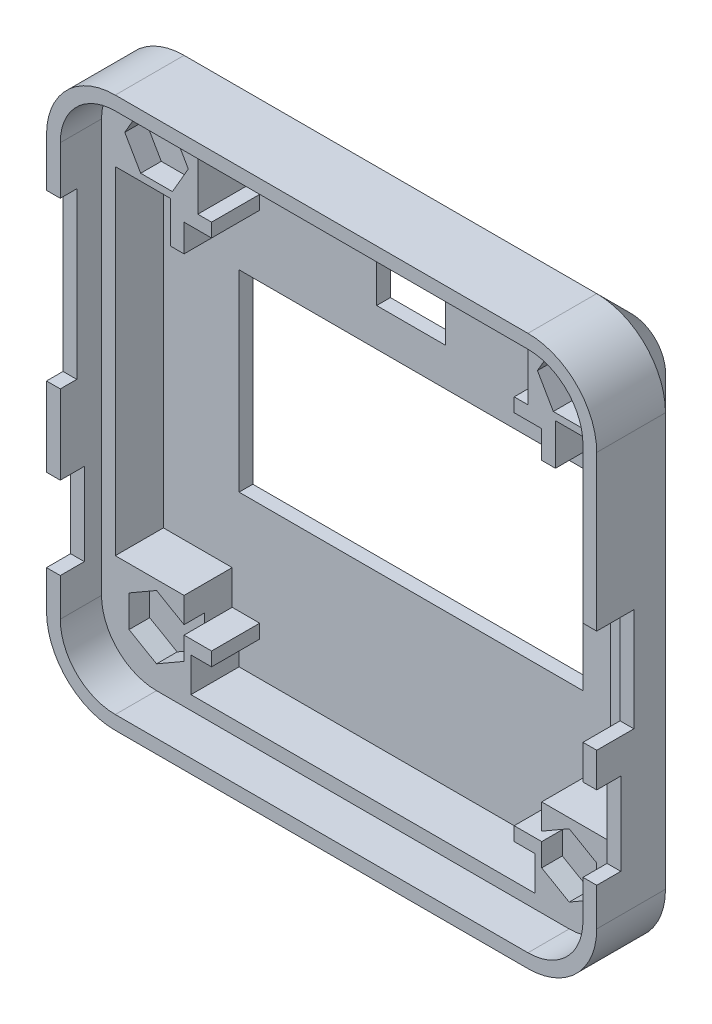
SolidWorks part; units mm, degrees
ref_plane "前基準面" through (0, 0, 0) normal (0, 0, 1) x (1, 0, 0)
ref_plane "上基準面" through (0, 0, 0) normal (0, 1, 0) x (1, 0, 0)
ref_plane "右基準面" through (0, 0, 0) normal (1, 0, 0) x (0, 0, -1)
sketch "草圖2" plane through (0, 0, -2.5) normal (0, 0, -1) x (-1, 0, 0)
  line L1 (0, 0) -> (1.8142, 0) construction
  line L2 (-15, -18.5) -> (15, -18.5)
  line L3 (-20, -13.5) -> (-20, 16.5)
  line L4 (-15, 21.5) -> (15, 21.5)
  line L5 (20, -13.5) -> (20, 16.5)
  line L6 (-20, -18.5) -> (20, 21.5) construction
  line L7 (-20, 21.5) -> (20, -18.5) construction
  arc A0 (-20, 16.5) -> (-15, 21.5) centre (-15, 16.5) cw
  arc A1 (15, -18.5) -> (20, -13.5) centre (15, -13.5) ccw
  arc A2 (-15, -18.5) -> (-20, -13.5) centre (-15, -13.5) cw
  arc A3 (15, 21.5) -> (20, 16.5) centre (15, 16.5) cw
  point P2 (0, 1.5)
  dimension "D3" = 5
  dimension "D1" = 40
  dimension "D2" = 40
  dimension "D4" = 1.5
extrude "填料-伸長1" add sketch "草圖2" along normal blind 1
sketch "草圖3" plane through (0, 0, -3.5) normal (0, 0, -1) x (-1, 0, 0)
  line L0 (0, 0) -> (5.3132, 0) construction
  line L1 (-12.5, -5.5) -> (12.5, -5.5)
  line L2 (-12.5, -5.5) -> (-12.5, 8.5)
  line L3 (-12.5, 8.5) -> (12.5, 8.5)
  line L4 (12.5, -5.5) -> (12.5, 8.5)
  line L5 (-12.5, -5.5) -> (12.5, 8.5) construction
  line L6 (-12.5, 8.5) -> (12.5, -5.5) construction
  point P0 (0, 1.5)
  dimension "D1" = 14
  dimension "D2" = 25
  dimension "D3" = 1.5
extrude "除料-伸長1" cut sketch "草圖3" against normal through all
sketch "草圖4" plane through (0, 0, -2.5) normal (0, 0, 1) x (1, 0, 0)
  line L16 (15, -18.5) -> (-15, -18.5) construction
  line L17 (-20, -13.5) -> (-20, 16.5) construction
  line L18 (-15, 21.5) -> (15, 21.5) construction
  line L19 (20, 16.5) -> (20, -13.5) construction
  line L20 (19, -13.5) -> (19, 16.5)
  line L21 (15, 20.5) -> (-15, 20.5)
  line L22 (-19, 16.5) -> (-19, -13.5)
  line L23 (-15, -17.5) -> (15, -17.5)
  line L24 (19, -13.5) -> (19, 16.5)
  line L25 (15, 20.5) -> (-15, 20.5)
  line L26 (-19, 16.5) -> (-19, -13.5)
  line L27 (-15, -17.5) -> (15, -17.5)
  line L28 (15, -18.5) -> (-15, -18.5)
  line L29 (-20, -13.5) -> (-20, 16.5)
  line L30 (-15, 21.5) -> (15, 21.5)
  line L31 (20, 16.5) -> (20, -13.5)
  arc A20 (-20, -13.5) -> (-15, -18.5) centre (-15, -13.5) ccw construction
  arc A21 (-15, 21.5) -> (-20, 16.5) centre (-15, 16.5) ccw construction
  arc A22 (20, 16.5) -> (15, 21.5) centre (15, 16.5) ccw construction
  arc A23 (15, -18.5) -> (20, -13.5) centre (15, -13.5) ccw construction
  arc A24 (19, 16.5) -> (15, 20.5) centre (15, 16.5) ccw
  arc A25 (-15, 20.5) -> (-19, 16.5) centre (-15, 16.5) ccw
  arc A26 (-19, -13.5) -> (-15, -17.5) centre (-15, -13.5) ccw
  arc A27 (15, -17.5) -> (19, -13.5) centre (15, -13.5) ccw
  arc A28 (19, 16.5) -> (15, 20.5) centre (15, 16.5) ccw
  arc A29 (-15, 20.5) -> (-19, 16.5) centre (-15, 16.5) ccw
  arc A30 (-19, -13.5) -> (-15, -17.5) centre (-15, -13.5) ccw
  arc A31 (15, -17.5) -> (19, -13.5) centre (15, -13.5) ccw
  arc A32 (-20, -13.5) -> (-15, -18.5) centre (-15, -13.5) ccw
  arc A33 (-15, 21.5) -> (-20, 16.5) centre (-15, 16.5) ccw
  arc A34 (20, 16.5) -> (15, 21.5) centre (15, 16.5) ccw
  arc A35 (15, -18.5) -> (20, -13.5) centre (15, -13.5) ccw
  dimension "D1" = 1
extrude "填料-伸長2" add sketch "草圖4" along normal blind 6.5
sketch "草圖5" plane through (0, 0, -2.5) normal (0, 0, 1) x (1, 0, 0)
  line L0 (18, -13.5) -> (18, 16.5)
  line L1 (15, 19.5) -> (-15, 19.5)
  line L2 (-18, 16.5) -> (-18, -13.5)
  line L3 (-15, -16.5) -> (15, -16.5)
  line L4 (19, -13.5) -> (19, 16.5)
  line L5 (15, 20.5) -> (-15, 20.5)
  line L6 (-19, 16.5) -> (-19, -13.5)
  line L7 (-15, -17.5) -> (15, -17.5)
  line L8 (19, -13.5) -> (19, 16.5)
  line L9 (15, 20.5) -> (-15, 20.5)
  line L10 (-19, 16.5) -> (-19, -13.5)
  line L11 (-15, -17.5) -> (15, -17.5)
  arc A0 (15, -16.5) -> (18, -13.5) centre (15, -13.5) ccw
  arc A1 (18, 16.5) -> (15, 19.5) centre (15, 16.5) ccw
  arc A2 (-15, 19.5) -> (-18, 16.5) centre (-15, 16.5) ccw
  arc A3 (-18, -13.5) -> (-15, -16.5) centre (-15, -13.5) ccw
  arc A4 (15, -17.5) -> (19, -13.5) centre (15, -13.5) ccw
  arc A5 (19, 16.5) -> (15, 20.5) centre (15, 16.5) ccw
  arc A6 (-15, 20.5) -> (-19, 16.5) centre (-15, 16.5) ccw
  arc A7 (-19, -13.5) -> (-15, -17.5) centre (-15, -13.5) ccw
  arc A8 (15, -17.5) -> (19, -13.5) centre (15, -13.5) ccw
  arc A9 (19, 16.5) -> (15, 20.5) centre (15, 16.5) ccw
  arc A10 (-15, 20.5) -> (-19, 16.5) centre (-15, 16.5) ccw
  arc A11 (-19, -13.5) -> (-15, -17.5) centre (-15, -13.5) ccw
  dimension "D1" = 0
  dimension "D2" = 1
extrude "填料-伸長3" add sketch "草圖5" along normal blind 3.5
sketch "草圖6" plane through (0, 0, -2.5) normal (0, 0, 1) x (1, 0, 0)
  line L0 (14, -14) -> (14, -10.5)
  line L1 (14, 14) -> (11, 14)
  line L2 (-14, 14) -> (-14, 11)
  line L3 (-14, -14) -> (-11, -14)
  line L4 (-13, -13) -> (13, -13)
  line L5 (-13, 13) -> (-13, -13)
  line L6 (13, 13) -> (-13, 13)
  line L7 (13, -13) -> (13, 13)
  line L8 (-13, -13) -> (-11, -13)
  line L9 (-13, 13) -> (-13, 11)
  line L10 (13, 13) -> (11, 13)
  line L11 (13, -13) -> (13, -10.5)
  line L12 (-11, 14) -> (-11, 13)
  line L13 (-13, 11) -> (-14, 11)
  line L14 (-13, -10.5) -> (-14, -10.5)
  line L15 (-11, -13) -> (-11, -14)
  line L16 (11, -13) -> (11, -14)
  line L17 (14, -10.5) -> (13, -10.5)
  line L18 (14, 11) -> (13, 11)
  line L19 (11, 14) -> (11, 13)
  line L20 (11, -14) -> (14, -14)
  line L21 (-14, -14) -> (14, -14) construction
  line L22 (11, -13) -> (13, -13)
  line L23 (-13, -13) -> (13, -13) construction
  line L24 (14, 11) -> (14, 14)
  line L25 (14, -14) -> (14, 14) construction
  line L26 (13, 11) -> (13, 13)
  line L27 (13, -13) -> (13, 13) construction
  line L28 (-11, 13) -> (-13, 13)
  line L29 (13, 13) -> (-13, 13) construction
  line L30 (-11, 14) -> (-14, 14)
  line L31 (14, 14) -> (-14, 14) construction
  line L32 (-13, -10.5) -> (-13, -13)
  line L33 (-13, 13) -> (-13, -13) construction
  line L34 (-14, -10.5) -> (-14, -14)
  line L35 (-14, 14) -> (-14, -14) construction
  dimension "D3" = 3
  dimension "D4" = 3
  dimension "D5" = 3.5
  dimension "D6" = 3
  dimension "D7" = 3
  dimension "D8" = 3.5
  dimension "D9" = 3
  dimension "D10" = 3
  dimension "D1" = 0
  dimension "D2" = 1
extrude "填料-伸長4" add sketch "草圖6" along normal blind 3.5
chamfer "導角1" distance 2.5 angle 45 8 edges at (-20, 1.5, -3.5) (-18.5355, 20.0355, -3.5) (-18.5355, -17.0355, -3.5) (0, 21.5, -3.5) (0, -18.5, -3.5) (18.5355, 20.0355, -3.5) (18.5355, -17.0355, -3.5) (20, 1.5, -3.5)
sketch "草圖7" plane through (0, 0, -2.5) normal (0, 0, 1) x (1, 0, 0)
  line L0 (-12, 19.5) -> (-12, 14)
  line L1 (15, 19.5) -> (-15, 19.5) construction
  line L2 (-11, 14) -> (-14, 14) construction
  line L3 (-12, 14) -> (-18, 14)
  line L4 (-18, 16.5) -> (-18, -13.5) construction
  line L5 (15, 19.5) -> (-15, 19.5) construction
  line L6 (-18, 16.5) -> (-18, -13.5) construction
  line L7 (-12, 19.5) -> (-15, 19.5)
  line L8 (-18, 16.5) -> (-18, 14)
  arc A0 (-15, 19.5) -> (-18, 16.5) centre (-15, 16.5) ccw construction
  arc A1 (-15, 19.5) -> (-18, 16.5) centre (-15, 16.5) ccw
  dimension "D1" = 6
extrude "填料-伸長5" add sketch "草圖7" along normal up to surface (3.5 mm away) up to face at (0, 1.5, 1)
sketch "草圖8" plane through (0, 0, -2.5) normal (0, 0, 1) x (1, 0, 0)
  line L0 (-12.5, -16.5) -> (-12.5, -14)
  line L1 (-15, -16.5) -> (15, -16.5) construction
  line L2 (-14, -14) -> (-11, -14) construction
  line L3 (-14, -10.5) -> (-18, -10.5)
  line L5 (-18, 14) -> (-18, -13.5) construction
  line L6 (-14, -14) -> (-11, -14) construction
  line L7 (-14, -10.5) -> (-14, -14) construction
  line L8 (-14, -14) -> (-12.5, -14)
  line L9 (-14, -10.5) -> (-14, -14)
  line L10 (-15, -16.5) -> (15, -16.5) construction
  line L11 (-18, 14) -> (-18, -13.5) construction
  line L12 (-15, -16.5) -> (-12.5, -16.5)
  line L13 (-18, -10.5) -> (-18, -13.5)
  arc A0 (-18, -13.5) -> (-15, -16.5) centre (-15, -13.5) ccw construction
  arc A1 (-18, -13.5) -> (-15, -16.5) centre (-15, -13.5) ccw
  dimension "D1" = 5.5
  dimension "D2" = 6
extrude "填料-伸長6" add sketch "草圖8" along normal up to surface (3.5 mm away) up to face at (0, 1.5, 1)
mirror "鏡射2" about plane through (0, 0, 0) normal (1, 0, 0) of "填料-伸長6", "填料-伸長5"
sketch "草圖10" plane through (0, 0, 1) normal (0, 0, 1) x (1, 0, 0)
  line L0 (-13, -13) -> (-13, -10.5) construction
  line L1 (-15, -15.8094) -> (-13, -14.6547)
  line L2 (-13, -14.6547) -> (-13, -12.3453)
  line L3 (-13, -12.3453) -> (-15, -11.1906)
  line L4 (-15, -11.1906) -> (-17, -12.3453)
  line L5 (-17, -12.3453) -> (-17, -14.6547)
  line L6 (-17, -14.6547) -> (-15, -15.8094)
  circle A0 centre (-15, -13.5) radius 2 construction
  dimension "D1" = 4
extrude "除料-伸長2" cut sketch "草圖10" against normal blind 1.5
sketch "草圖11" plane through (0, 0, 1) normal (0, 0, 1) x (1, 0, 0)
  line L0 (-18, 14) -> (-14, 14) construction
  line L1 (-17.3094, 16.5) -> (-16.1547, 14.5)
  line L2 (-16.1547, 14.5) -> (-13.8453, 14.5)
  line L3 (-13.8453, 14.5) -> (-12.6906, 16.5)
  line L4 (-12.6906, 16.5) -> (-13.8453, 18.5)
  line L5 (-13.8453, 18.5) -> (-16.1547, 18.5)
  line L6 (-16.1547, 18.5) -> (-17.3094, 16.5)
  circle A0 centre (-15, 16.5) radius 2 construction
  dimension "D1" = 4
extrude "除料-伸長3" cut sketch "草圖11" against normal blind 1.5
mirror "鏡射3" about plane through (0, 0, 0) normal (1, 0, 0) of "除料-伸長3", "除料-伸長2"
sketch "草圖12" plane through (20, 0, 0) normal (1, 0, 0) x (0, 0, -1)
  line L0 (-4, 1.5) -> (8.2769, 1.5) construction
  line L1 (-4, -13.5) -> (-4, 16.5) construction
  line L2 (1, -13.5) -> (-4, -13.5) construction
  line L3 (1, 16.5) -> (-4, 16.5) construction
  line L4 (-4, -10.75) -> (-4, -4.75)
  line L11 (-4, -10.75) -> (-2.25, -10.75)
  line L12 (-2.25, -10.75) -> (-2.25, -4.75)
  line L13 (-4, -4.75) -> (-2.25, -4.75)
  line L15 (-1.3, 5.25) -> (-4, 5.25)
  line L16 (-1.3, 5.25) -> (-1.3, -2.25)
  line L17 (-1.3, -2.25) -> (-4, -2.25)
  line L18 (-4, 5.25) -> (-4, -2.25)
  line L19 (-1.3, 5.25) -> (-4, -2.25) construction
  line L20 (-1.3, -2.25) -> (-4, 5.25) construction
  point P17 (-2.65, 1.5)
  line M15 (-4, 16.5) -> (-4, -13.5)
  dimension "D4" = 7.5
  dimension "D5" = 2.7
  dimension "D6" = 0
extrude "除料-伸長4" cut sketch "草圖12" against normal up to next
sketch "草圖13" plane through (-20, 0, 0) normal (-1, 0, 0) x (0, 0, 1)
  line L0 (0, 0) -> (4.5847, 0) construction
  line L1 (4, 16.5) -> (4, -13.5) construction
  line L2 (4, 1) -> (2.8, 1)
  line L3 (4, 1) -> (4, 13)
  line L4 (4, 13) -> (2.8, 13)
  line L5 (2.8, 1) -> (2.8, 13)
  line L6 (4, 7) -> (0.2085, 7) construction
  dimension "D1" = 12
  dimension "D2" = 1.2
  dimension "D3" = 7
extrude "除料-伸長5" cut sketch "草圖13" against normal up to next
sketch "草圖14" plane through (0, 0, -3.5) normal (0, 0, -1) x (-1, 0, 0)
  line L0 (-5.0391, 13.75) -> (5.7543, 13.75) construction
  line L1 (-2.5, 11.25) -> (2.5, 11.25)
  line L2 (-2.5, 11.25) -> (-2.5, 16.25)
  line L3 (-2.5, 16.25) -> (2.5, 16.25)
  line L4 (2.5, 11.25) -> (2.5, 16.25)
  line L5 (-2.5, 11.25) -> (2.5, 16.25) construction
  line L6 (-2.5, 16.25) -> (2.5, 11.25) construction
  line L7 (15, 19) -> (-15, 19) construction
  line L8 (12.5, 8.5) -> (-12.5, 8.5) construction
  point P0 (0, 13.75)
  dimension "D1" = 5
  dimension "D2" = 5
extrude "除料-伸長6" cut sketch "草圖14" against normal blind 1.5
extrude "除料-伸長7" cut sketch "草圖12<2>" against normal through all contours L13 L11 L12 M15 region at (20, -7.75, 3.125)
sketch "草圖12<2>" plane through (20, 0, 0) normal (1, 0, 0) x (0, 0, -1) same geometry as "草圖12"
